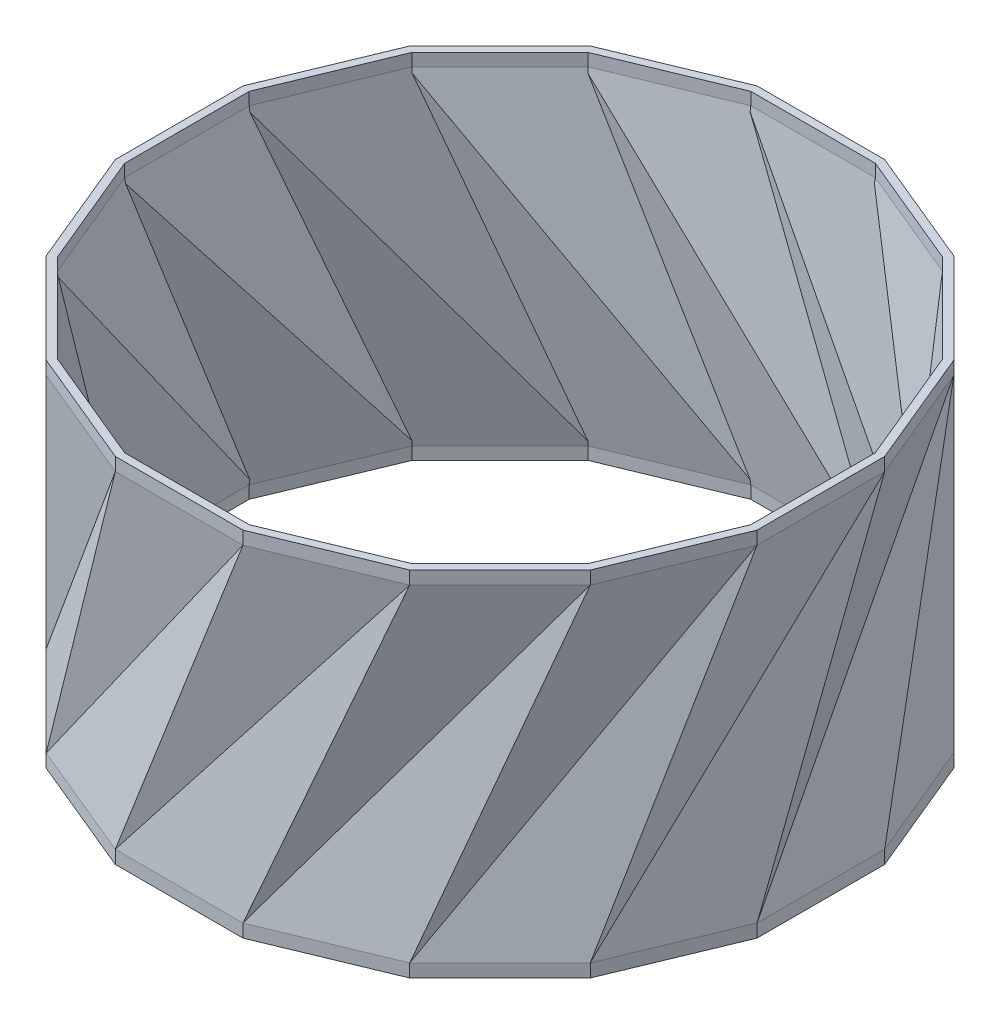
SolidWorks part; units mm, degrees
ref_plane "정면" through (0, 0, 0) normal (0, 0, 1) x (1, 0, 0)
ref_plane "윗면" through (0, 0, 0) normal (0, 1, 0) x (1, 0, 0)
ref_plane "우측면" through (0, 0, 0) normal (1, 0, 0) x (0, 0, -1)
sketch "스케치1" plane through (0, 0, 0) normal (0, 1, 0) x (1, 0, 0)
  line L0 (-55, 0) -> (55, 0) construction
  line L1 (20.7867, -13.8893) -> (24.5196, -4.8773)
  line L2 (24.5196, -4.8773) -> (24.5196, 4.8773)
  line L3 (24.5196, 4.8773) -> (20.7867, 13.8893)
  line L4 (20.7867, 13.8893) -> (13.8893, 20.7867)
  line L5 (13.8893, 20.7867) -> (4.8773, 24.5196)
  line L6 (4.8773, 24.5196) -> (-4.8773, 24.5196)
  line L7 (-4.8773, 24.5196) -> (-13.8893, 20.7867)
  line L8 (-13.8893, 20.7867) -> (-20.7867, 13.8893)
  line L9 (-20.7867, 13.8893) -> (-24.5196, 4.8773)
  line L10 (-24.5196, 4.8773) -> (-24.5196, -4.8773)
  line L11 (-24.5196, -4.8773) -> (-20.7867, -13.8893)
  line L12 (-20.7867, -13.8893) -> (-13.8893, -20.7867)
  line L13 (-13.8893, -20.7867) -> (-4.8773, -24.5196)
  line L14 (-4.8773, -24.5196) -> (4.8773, -24.5196)
  line L15 (4.8773, -24.5196) -> (13.8893, -20.7867)
  line L16 (13.8893, -20.7867) -> (20.7867, -13.8893)
  circle A0 centre (0, 0) radius 25 construction
  dimension "D1" = 50
extrude "보스-돌출1" add sketch "스케치1" along normal blind 25
ref_plane "평면1" through (0, 3.5813, 23.9849) normal (0, 0.1477, 0.989) x (1, 0, 0)
sketch "스케치2" plane through (0, 3.5813, 23.9849) normal (0, 0.1477, 0.989) x (1, 0, 0)
  line L0 (-4.8773, -3.621) -> (13.8893, 21.6561)
  line L1 (13.8893, 21.6561) -> (4.8773, -3.621)
sketch "스케치3" plane through (0, 0, 24.5196) normal (0, 0, 1) x (1, 0, 0)
  line L0 (-4.8773, 0) -> (4.8773, 25)
ref_plane "평면2" through (-4.8773, 0, 24.5196) normal (0.5961, 0.7941, -0.1186) x (0.8029, -0.5896, 0.088)
sketch "스케치4" plane through (-4.8773, 0, 24.5196) normal (0.5961, 0.7941, -0.1186) x (0.8029, -0.5896, 0.088)
  line L0 (0, 0) -> (-6.9072, -3.692) construction
  line L1 (0, 0) -> (7.832, 0) construction
  line L2 (0, 0) -> (-6.9072, -3.692)
  line L3 (0, 0) -> (7.832, 0)
  line L4 (-6.9072, -3.692) -> (7.832, 0)
extrude "컷-돌출1" cut sketch "스케치4" along normal up to vertex (31.482 mm away) up to point (13.8893, 25, 20.7867)
pattern_circular "원형 패턴1" count 16 over 360 about axis through (0, 25, 0) along (0, 1, 0) of "컷-돌출1"
sketch "스케치5" plane through (0, 25, 0) normal (0, 1, 0) x (1, 0, 0)
  line L16 (13.8893, -20.7867) -> (20.7867, -13.8893)
  line L17 (20.7867, -13.8893) -> (24.5196, -4.8773)
  line L18 (24.5196, -4.8773) -> (24.5196, 4.8773)
  line L19 (24.5196, 4.8773) -> (20.7867, 13.8893)
  line L20 (20.7867, 13.8893) -> (13.8893, 20.7867)
  line L21 (13.8893, 20.7867) -> (4.8773, 24.5196)
  line L22 (4.8773, 24.5196) -> (-4.8773, 24.5196)
  line L23 (-4.8773, 24.5196) -> (-13.8893, 20.7867)
  line L24 (-13.8893, 20.7867) -> (-20.7867, 13.8893)
  line L25 (-20.7867, 13.8893) -> (-24.5196, 4.8773)
  line L26 (-24.5196, 4.8773) -> (-24.5196, -4.8773)
  line L27 (-24.5196, -4.8773) -> (-20.7867, -13.8893)
  line L28 (-20.7867, -13.8893) -> (-13.8893, -20.7867)
  line L29 (-13.8893, -20.7867) -> (-4.8773, -24.5196)
  line L30 (-4.8773, -24.5196) -> (4.8773, -24.5196)
  line L31 (4.8773, -24.5196) -> (13.8893, -20.7867)
  line L32 (13.8893, -20.7867) -> (20.7867, -13.8893)
  line L33 (20.7867, -13.8893) -> (24.5196, -4.8773)
  line L34 (24.5196, -4.8773) -> (24.5196, 4.8773)
  line L35 (24.5196, 4.8773) -> (20.7867, 13.8893)
  line L36 (20.7867, 13.8893) -> (13.8893, 20.7867)
  line L37 (13.8893, 20.7867) -> (4.8773, 24.5196)
  line L38 (4.8773, 24.5196) -> (-4.8773, 24.5196)
  line L39 (-4.8773, 24.5196) -> (-13.8893, 20.7867)
  line L40 (-13.8893, 20.7867) -> (-20.7867, 13.8893)
  line L41 (-20.7867, 13.8893) -> (-24.5196, 4.8773)
  line L42 (-24.5196, 4.8773) -> (-24.5196, -4.8773)
  line L43 (-24.5196, -4.8773) -> (-20.7867, -13.8893)
  line L44 (-20.7867, -13.8893) -> (-13.8893, -20.7867)
  line L45 (-13.8893, -20.7867) -> (-4.8773, -24.5196)
  line L46 (-4.8773, -24.5196) -> (4.8773, -24.5196)
  line L47 (4.8773, -24.5196) -> (13.8893, -20.7867)
  dimension "D1" = 0
extrude "보스-돌출2" add sketch "스케치5" along normal blind 1
sketch "스케치6" plane through (0, 0, 0) normal (0, -1, 0) x (1, 0, 0)
  line L16 (20.7867, 13.8893) -> (13.8893, 20.7867)
  line L17 (13.8893, 20.7867) -> (4.8773, 24.5196)
  line L18 (4.8773, 24.5196) -> (-4.8773, 24.5196)
  line L19 (-4.8773, 24.5196) -> (-13.8893, 20.7867)
  line L20 (-13.8893, 20.7867) -> (-20.7867, 13.8893)
  line L21 (-20.7867, 13.8893) -> (-24.5196, 4.8773)
  line L22 (-24.5196, 4.8773) -> (-24.5196, -4.8773)
  line L23 (-24.5196, -4.8773) -> (-20.7867, -13.8893)
  line L24 (-20.7867, -13.8893) -> (-13.8893, -20.7867)
  line L25 (-13.8893, -20.7867) -> (-4.8773, -24.5196)
  line L26 (-4.8773, -24.5196) -> (4.8773, -24.5196)
  line L27 (4.8773, -24.5196) -> (13.8893, -20.7867)
  line L28 (13.8893, -20.7867) -> (20.7867, -13.8893)
  line L29 (20.7867, -13.8893) -> (24.5196, -4.8773)
  line L30 (24.5196, -4.8773) -> (24.5196, 4.8773)
  line L31 (24.5196, 4.8773) -> (20.7867, 13.8893)
  line L32 (20.7867, 13.8893) -> (13.8893, 20.7867)
  line L33 (13.8893, 20.7867) -> (4.8773, 24.5196)
  line L34 (4.8773, 24.5196) -> (-4.8773, 24.5196)
  line L35 (-4.8773, 24.5196) -> (-13.8893, 20.7867)
  line L36 (-13.8893, 20.7867) -> (-20.7867, 13.8893)
  line L37 (-20.7867, 13.8893) -> (-24.5196, 4.8773)
  line L38 (-24.5196, 4.8773) -> (-24.5196, -4.8773)
  line L39 (-24.5196, -4.8773) -> (-20.7867, -13.8893)
  line L40 (-20.7867, -13.8893) -> (-13.8893, -20.7867)
  line L41 (-13.8893, -20.7867) -> (-4.8773, -24.5196)
  line L42 (-4.8773, -24.5196) -> (4.8773, -24.5196)
  line L43 (4.8773, -24.5196) -> (13.8893, -20.7867)
  line L44 (13.8893, -20.7867) -> (20.7867, -13.8893)
  line L45 (20.7867, -13.8893) -> (24.5196, -4.8773)
  line L46 (24.5196, -4.8773) -> (24.5196, 4.8773)
  line L47 (24.5196, 4.8773) -> (20.7867, 13.8893)
  dimension "D1" = 0
extrude "보스-돌출3" add sketch "스케치6" along normal blind 1
shell "쉘1" thickness 0.6 removed face at (0, -1, 0) removed face at (0, 26, 0)
